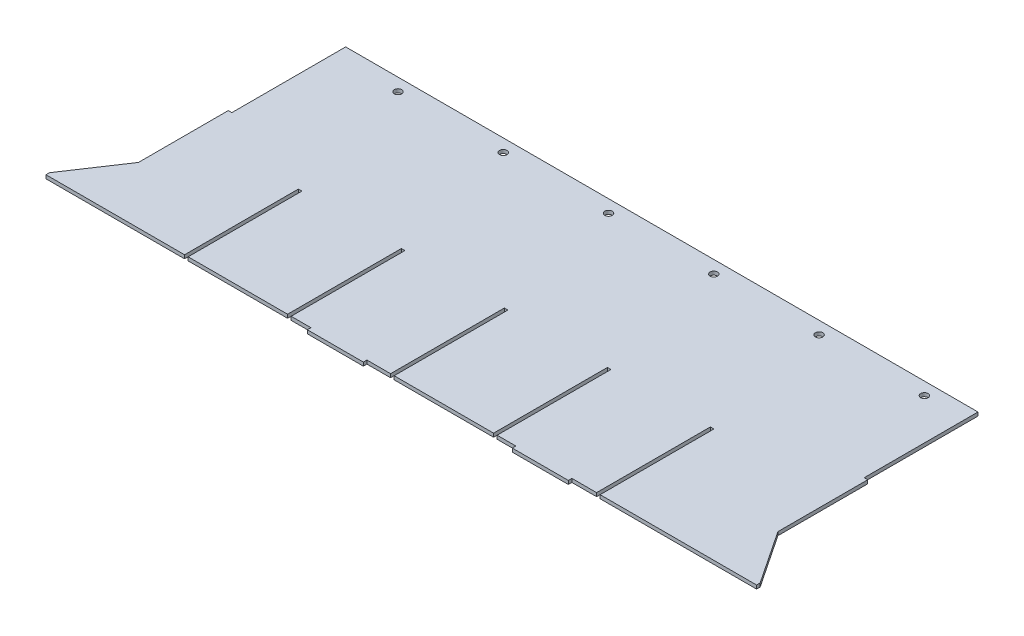
SolidWorks part; units mm, degrees
material "6061-T6 (SS)"
ref_plane "X-Y Datum" through (0, 0, 0) normal (0, 0, 1) x (1, 0, 0)
ref_plane "X-Z Datum" through (0, 0, 0) normal (0, 1, 0) x (1, 0, 0)
ref_plane "Y-Z Datum" through (0, 0, 0) normal (1, 0, 0) x (0, 0, -1)
sketch "Sketch1" plane through (0, 0, 0) normal (0, 0, 1) x (1, 0, 0)
  line L1 (-285.4305, -1.5875) -> (285.4305, -1.5875)
  line L2 (-285.4305, -1.5875) -> (-285.4305, 1.5875)
  line L3 (-285.4305, 1.5875) -> (285.4305, 1.5875)
  line L4 (285.4305, -1.5875) -> (285.4305, 1.5875)
  line L5 (-285.4305, -1.5875) -> (285.4305, 1.5875) construction
  line L6 (-285.4305, 1.5875) -> (285.4305, -1.5875) construction
  point P0 (0, 0)
  dimension "D1" = 570.861
  dimension "D2" = 3.175
extrude "Boss-Extrude1" add sketch "Sketch1" along normal blind 232.6
sketch "Sketch2" plane through (0, 1.5875, 0) normal (0, 1, 0) x (1, 0, 0)
  line L0 (-176.5505, -181.8) -> (-285.4305, -181.8) construction
  line L1 (-285.4305, -232.6) -> (-285.4305, 0) construction
  line L3 (285.4305, -232.6) -> (-285.4305, -232.6) construction
  line L4 (-178.0615, -232.6) -> (-174.8865, -232.6)
  line L6 (-178.0615, -118.3) -> (-174.8865, -118.3)
  line L8 (-178.0615, -232.6) -> (-174.8865, -232.6)
  line L9 (-178.0615, -232.6) -> (-178.0615, -118.3)
  line L10 (-178.0615, -118.3) -> (-174.8865, -118.3)
  line L11 (-174.8865, -232.6) -> (-174.8865, -118.3)
  line L17 (-178.0615, -118.3) -> (-174.8865, -118.3)
  line L38 (-285.4305, 0) -> (-282.2555, 0)
  line L39 (-285.4305, 0) -> (-285.4305, -101.6)
  line L40 (-285.4305, -101.6) -> (-282.2555, -101.6)
  line L41 (-282.2555, 0) -> (-282.2555, -101.6)
  line L42 (285.4305, 0) -> (282.2555, 0)
  line L43 (285.4305, 0) -> (285.4305, -101.6)
  line L44 (285.4305, -101.6) -> (282.2555, -101.6)
  line L45 (282.2555, 0) -> (282.2555, -101.6)
  line M3 (285.4305, 0) -> (-285.4305, 0)
  line M4 (-285.4305, 0) -> (-285.4305, -232.6)
  line M6 (285.4305, -232.6) -> (285.4305, 0)
  dimension "D2" = 50.8
  dimension "D3" = 3.175
  dimension "D6" = 3.175
  dimension "D7" = 101.6
  dimension "D4" = 114.3
  dimension "D8" = 3.175
  dimension "D9" = 101.6
sketch "Sketch6" plane through (0, 0, 232.6) normal (0, 0, 1) x (1, 0, 0)
  line L0 (285.4305, 1.5875) -> (-285.4305, 1.5875) construction
  line L1 (-285.4305, 1.5875) -> (-285.4305, -1.5875) construction
  line L14 (152.263, -1.5875) -> (152.263, 1.5875)
  line L15 (102.263, 1.5875) -> (152.263, 1.5875)
  line L16 (102.263, -1.5875) -> (152.263, 1.5875) construction
  line L17 (102.263, 1.5875) -> (152.263, -1.5875) construction
  line L18 (102.263, -1.5875) -> (152.263, -1.5875)
  line L19 (102.263, -1.5875) -> (102.263, 1.5875)
  line L20 (-30.6951, -1.5875) -> (-30.6951, 1.5875)
  line L21 (-80.6951, 1.5875) -> (-30.6951, 1.5875)
  line L22 (-80.6951, -1.5875) -> (-30.6951, 1.5875) construction
  line L23 (-80.6951, 1.5875) -> (-30.6951, -1.5875) construction
  line L24 (-80.6951, -1.5875) -> (-30.6951, -1.5875)
  line L25 (-80.6951, -1.5875) -> (-80.6951, 1.5875)
  point P4 (-55.6951, 0)
  point P5 (127.263, 0)
  dimension "D1" = 3.175
  dimension "D2" = 50
  dimension "D3" = 3.175
  dimension "D4" = 229.7354
  dimension "D5" = 182.9581
sketch "Sketch7" plane through (0, -1.5875, 0) normal (0, -1, 0) x (-1, 0, 0)
  line L1 (-285.4305, -232.6) -> (-285.4305, 0) construction
  circle A2 centre (-245.6805, -11.2916) radius 3.302
  dimension "D1" = 39.75
  dimension "D2" = 6.604
extrude "Cut-Extrude4" cut sketch "Sketch7" against normal through all contours A2 region at (245.6805, -1.5875, 11.2916)
extrude "Boss-Extrude2" add sketch "Sketch6" along normal blind 3.175
pattern_linear "LPattern1" count 6 spacing 93.98 along (-1, 0, 0) of "Cut-Extrude4"
extrude "Cut-Extrude5" cut sketch "Sketch2" against normal through all contours L41 L40 M3 M4 | L45 L44 M3 M6 region at (283.843, 1.5875, 50.8) region at (-283.843, 1.5875, 50.8)
sketch "Sketch12" plane through (0, 1.5875, 0) normal (0, 1, 0) x (1, 0, 0)
  line L0 (-285.4305, -232.6) -> (-285.4305, -101.6) construction
  line L1 (-285.4305, -232.6) -> (-285.4305, -181.8)
  line L2 (285.4305, -232.6) -> (285.4305, -101.6) construction
  line L3 (285.4305, -232.6) -> (285.4305, -101.6)
  line L4 (-285.4305, -232.6) -> (-317.1805, -232.6)
  line L6 (-317.1805, -232.6) -> (-317.1805, -229.425)
  line L7 (-317.1805, -229.425) -> (-285.4305, -181.8)
  line M9 (-285.4305, -101.6) -> (-285.4305, -232.6)
  dimension "D1" = 31.75
  dimension "D2" = 50.8
  dimension "D3" = 3.175
extrude "Boss-Extrude3" add sketch "Sketch12" against normal blind 3.175 contours L4 M9 region at (-296.6364, 1.5875, 215.6044)
mirror "Mirror1" about plane through (0, 0, 0) normal (1, 0, 0) of "Boss-Extrude3"
sketch "Sketch13" plane through (0, -1.5875, 0) normal (0, -1, 0) x (1, 0, 0)
  line L0 (-193.4755, 232.6) -> (-193.4755, 131)
  line L1 (-317.1805, 232.6) -> (-80.6951, 232.6) construction
  line L2 (-282.2555, 0) -> (-282.2555, 101.6) construction
  line L3 (-193.4755, 232.6) -> (-190.3005, 232.6)
  line L5 (-193.4755, 232.6) -> (-193.4755, 131)
  line L6 (-193.4755, 131) -> (-190.3005, 131)
  line L7 (-190.3005, 232.6) -> (-190.3005, 131)
  line M23 (-80.6951, 232.6) -> (-317.1805, 232.6)
  dimension "D1" = 88.78
  dimension "D2" = 101.6
  dimension "D3" = 3.175
extrude "Cut-Extrude6" cut sketch "Sketch13" against normal through all contours L7 L0 L6 M23 region at (-191.888, -1.5875, 181.8)
pattern_linear "LPattern2" count 5 spacing 91.955 along (1, 0, 0) of "Cut-Extrude6"
